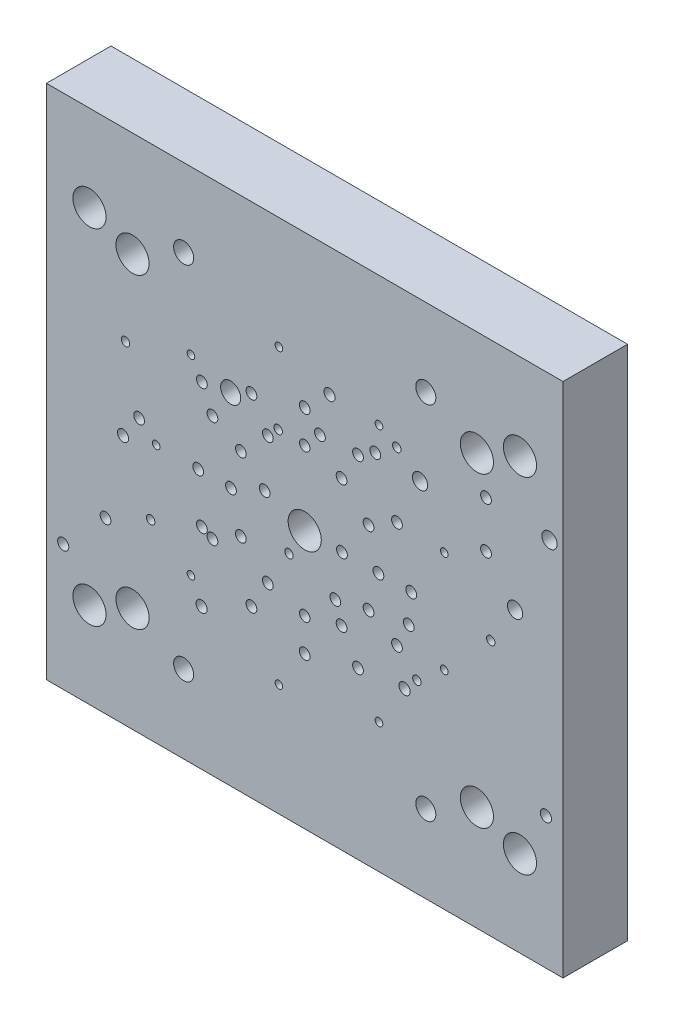
SolidWorks part; units mm, degrees
ref_plane "Front Plane" through (0, 0, 0) normal (0, 0, 1) x (1, 0, 0)
ref_plane "Top Plane" through (0, 0, 0) normal (0, 1, 0) x (1, 0, 0)
ref_plane "Right Plane" through (0, 0, 0) normal (1, 0, 0) x (0, 0, -1)
sketch "Sketch1" plane through (0, 0, 0) normal (0, 0, 1) x (1, 0, 0)
  line L1 (-152.4, 152.4) -> (152.4, 152.4)
  line L2 (-152.4, 152.4) -> (-152.4, -152.4)
  line L3 (-152.4, -152.4) -> (152.4, -152.4)
  line L4 (152.4, 152.4) -> (152.4, -152.4)
  line L5 (-152.4, 152.4) -> (152.4, -152.4) construction
  line L6 (-152.4, -152.4) -> (152.4, 152.4) construction
  point P0 (0, 0)
  dimension "D1" = 304.8
  dimension "D2" = 304.8
extrude "Boss-Extrude1" add sketch "Sketch1" along normal blind 38.1
sketch "Sketch2" plane through (0, 0, 38.1) normal (0, 0, 1) x (1, 0, 0)
  line L0 (-152.4, 0) -> (152.4, 0) construction
  line L5 (-152.4, 152.4) -> (-152.4, -152.4) construction
  line L6 (152.4, -152.4) -> (152.4, 152.4) construction
  line L7 (-152.4, -101.6) -> (152.4, -101.6) construction
  line L8 (-152.4, 101.6) -> (152.4, 101.6) construction
  line L9 (0, 101.6) -> (0, -101.6) construction
  line L10 (127, 101.6) -> (127, -101.6) construction
  line L11 (-127, 101.6) -> (-127, -101.6) construction
  circle A0 centre (-127, 101.6) radius 6.5151
  circle A1 centre (127, 101.6) radius 6.5151
  circle A2 centre (127, -101.6) radius 6.5151
  circle A3 centre (-127, -101.6) radius 6.5151
  circle A4 centre (0, 0) radius 6.5151
  dimension "D5" = 13.0302
  dimension "D1" = 101.6
  dimension "D2" = 101.6
  dimension "D3" = 127
  dimension "D4" = 127
extrude "HAAS T-Slot Holes" cut sketch "Sketch2" against normal through all
sketch "Sketch3" plane through (0, 0, 38.1) normal (0, 0, 1) x (1, 0, 0)
  circle A0 centre (-127, 101.6) radius 9.779
  circle A1 centre (127, 101.6) radius 9.779
  circle A2 centre (0, 0) radius 9.779
  circle A3 centre (127, -101.6) radius 9.779
  circle A4 centre (-127, -101.6) radius 9.779
  dimension "D1" = 19.558
extrude "HAAS Counter Bores" cut sketch "Sketch3" against normal offset from surface (22.225 mm away) 15.875 contours A0 | A1 | A2 | A3 | A4 up to face at (6.5151, 0, 0)
sketch "Sketch4" plane through (0, 0, 38.1) normal (0, 0, 1) x (1, 0, 0)
  line L0 (-127, 90.4875) -> (127, 90.4875) construction
  line L1 (-127, 30.1625) -> (127, 30.1625) construction
  line L2 (-127, 30.1625) -> (-127, -30.1625) construction
  line L3 (-127, -30.1625) -> (127, -30.1625) construction
  line L4 (127, 30.1625) -> (127, -30.1625) construction
  line L5 (-127, 30.1625) -> (127, -30.1625) construction
  line L6 (-127, -30.1625) -> (127, 30.1625) construction
  line L7 (-127, -90.4875) -> (127, -90.4875) construction
  line L8 (-101.6, 90.4875) -> (-101.6, 84.1375) construction
  line L9 (-101.6, -90.4875) -> (-101.6, -84.1375) construction
  line L10 (101.6, -90.4875) -> (101.6, -84.1375) construction
  line L11 (101.6, 90.4875) -> (101.6, 84.1375) construction
  circle A0 centre (-101.6, 90.4875) radius 6.5151
  circle A1 centre (101.6, 90.4875) radius 6.5151
  circle A2 centre (-101.6, -90.4875) radius 6.5151
  circle A3 centre (101.6, -90.4875) radius 6.5151
  point P0 (0, 0)
  dimension "D9" = 13.0302
  dimension "D1" = 60.325
  dimension "D2" = 254
  dimension "D5" = 203.2
  dimension "D6" = 25.4
  dimension "D7" = 203.2
  dimension "D8" = 6.35
  dimension "D3" = 60.325
  dimension "D4" = 60.325
extrude "Tormach T-Slot Holes" cut sketch "Sketch4" against normal through all
sketch "Sketch5" plane through (0, 0, 38.1) normal (0, 0, 1) x (1, 0, 0)
  circle A0 centre (-101.6, 90.4875) radius 9.779
  circle A1 centre (101.6, 90.4875) radius 9.779
  circle A2 centre (101.6, -90.4875) radius 9.779
  circle A3 centre (-101.6, -90.4875) radius 9.779
  dimension "D1" = 19.558
extrude "Tormach Counter bores" cut sketch "Sketch5" against normal up to surface (22.225 mm away) up to face at (-117.221, 101.6, 15.875)
sketch "Sketch6" plane through (0, 0, 38.1) normal (0, 0, 1) x (1, 0, 0)
  circle A0 centre (0, 0) radius 43.5 construction
  circle A1 centre (0, 43.5) radius 3.0734
  circle A2 centre (0, -43.5) radius 3.0734
  dimension "D1" = 87.0001
  dimension "D2" = 6.1468
extrude "Sprocket Locating Holes" cut sketch "Sketch6" against normal blind 6.35
sketch "Sketch7" plane through (0, 0, 38.1) normal (0, 0, 1) x (1, 0, 0)
  circle A0 centre (0, 0) radius 43.5 construction
  circle A2 centre (43.5, 0) radius 3.175
  circle A4 centre (37.6721, -21.75) radius 3.175
  circle A5 centre (21.75, -37.6721) radius 3.175
  circle A6 centre (0, -43.5) radius 3.175 [skipped]
  circle A7 centre (-21.75, -37.6721) radius 3.175
  circle A8 centre (-37.6721, -21.75) radius 3.175
  circle A9 centre (-43.5, 0) radius 3.175
  circle A10 centre (-37.6721, 21.75) radius 3.175
  circle A11 centre (-21.75, 37.6721) radius 3.175
  circle A12 centre (0, 43.5) radius 3.175 [skipped]
  circle A13 centre (21.75, 37.6721) radius 3.175
  circle A14 centre (37.6721, 21.75) radius 3.175
  point P31 (0, 0)
  dimension "D1" = 87.0001
  dimension "D2" = 6.35
  dimension "D3" = 12
extrude "Sprocket Mounting clearance holes" cut sketch "Sketch7" against normal blind 9.525
sketch "Sketch8" plane through (0, 0, 38.1) normal (0, 0, 1) x (1, 0, 0)
  line L1 (-71.4375, 106.4641) -> (71.4375, 106.4641) construction
  line L2 (-71.4375, 106.4641) -> (-71.4375, -106.4641) construction
  line L3 (-71.4375, -106.4641) -> (71.4375, -106.4641) construction
  line L4 (71.4375, 106.4641) -> (71.4375, -106.4641) construction
  line L5 (-71.4375, 106.4641) -> (71.4375, -106.4641) construction
  line L6 (-71.4375, -106.4641) -> (71.4375, 106.4641) construction
  circle A0 centre (-71.4375, 106.4641) radius 5.9182
  circle A1 centre (71.4375, 106.4641) radius 5.9182
  circle A2 centre (71.4375, -106.4641) radius 5.9182
  circle A3 centre (-71.4375, -106.4641) radius 5.9182
  point P0 (0, 0)
  dimension "D3" = 11.8364
  dimension "D1" = 142.875
  dimension "D2" = 212.9282
extrude "1/2-13 Tapped Holes" cut sketch "Sketch8" against normal blind 19.05
sketch "Sketch9" plane through (0, 0, 38.1) normal (0, 0, 1) x (1, 0, 0)
  circle A0 centre (-117.5189, -52.2876) radius 3.175
  circle A1 centre (-60.6634, -28.4101) radius 3.175
  circle A2 centre (-60.6634, 45.677) radius 3.175
  circle A3 centre (-23.6198, 8.6335) radius 3.175
  circle A4 centre (-97.707, 8.6335) radius 3.175
  circle A5 centre (18.0623, -26.1797) radius 3.175
  circle A6 centre (21.9762, 0) radius 3.175
  circle A7 centre (61.3833, -17.3739) radius 3.175
  circle A8 centre (106.976, 70.3959) radius 3.175
  circle A9 centre (106.976, 42.9004) radius 3.175
  circle A10 centre (144.4539, 67.4373) radius 4.5
  circle A11 centre (124.1092, 21.6131) radius 4.5
  circle A12 centre (68.0681, 59.3279) radius 4.5
  circle A13 centre (58.9353, -51.2652) radius 3.3
  circle A14 centre (-142.4923, -78.095) radius 3.3
  circle A15 centre (-105.7351, 43.7713) radius 2.5
  circle A16 centre (-90.8975, -39.8642) radius 2.5
  circle A17 centre (-9.2711, -16.3656) radius 2.5
  circle A18 centre (-15.6655, 43.8657) radius 2.5
  circle A20 centre (14.6267, 76.8405) radius 3.3
  circle A21 centre (8.9855, 53.4682) radius 3.175
  circle A22 centre (41.6559, 60.6579) radius 3.175
extrude "SSB Holes" cut sketch "Sketch9" against normal blind 19.05
ref_axis "Axis1" through (0, 0, 0) along (0, 0, 1)
sketch "Sketch10" plane through (0, 0, 38.1) normal (0, 0, 1) x (1, 0, 0)
  circle A0 centre (0, 0) radius 62.865 construction
  circle A1 centre (0, 62.865) radius 3.175
  circle A13 centre (31.4325, 54.4427) radius 3.175
  circle A14 centre (54.4427, 31.4325) radius 3.175
  circle A15 centre (62.865, 0) radius 3.175
  circle A16 centre (54.4427, -31.4325) radius 3.175
  circle A17 centre (31.4325, -54.4427) radius 3.175
  circle A18 centre (0, -62.865) radius 3.175
  circle A19 centre (-31.4325, -54.4427) radius 3.175
  circle A20 centre (-54.4427, -31.4325) radius 3.175
  circle A21 centre (-62.865, 0) radius 3.175
  circle A22 centre (-54.4427, 31.4325) radius 3.175
  circle A23 centre (-31.4325, 54.4427) radius 3.175
  point P30 (0, 0)
  point P56 (0, 0)
  dimension "D1" = 125.73
  dimension "D2" = 6.35
  dimension "D4" = 12
extrude "Sprocket Countersunk Holes" cut sketch "Sketch10" against normal blind 19.05
sketch "Sketch12" plane through (0, 0, 38.1) normal (0, 0, 1) x (1, 0, 0)
  circle A0 centre (-107.2144, -4.9977) radius 3.3
  circle A1 centre (-60.8212, -69.1392) radius 3.3
  circle A2 centre (142.3129, -74.567) radius 3.3
  circle A4 centre (54.3307, 69.7186) radius 2.4964
  circle A5 centre (109.7823, -1.2607) radius 2.5
  circle A6 centre (66.2094, -43.3332) radius 2.5
  circle A7 centre (-43.6886, 48.7489) radius 5.9182
  circle A8 centre (-71.4375, 106.4641) radius 5.9182 construction
extrude "DSB Holes" cut sketch "Sketch12" against normal blind 19.05
sketch "Brake Rotor Toe Clamp Holes" plane through (0, 0, 38.1) normal (0, 0, 1) x (1, 0, 0)
  line L0 (-74.6653, 106.6331) -> (74.6653, -106.6331) construction
  line L1 (74.6653, 106.6331) -> (-74.6653, -106.6331) construction
  line L6 (0, 0) -> (192.0367, 0) construction
  line L7 (0, 0) -> (-160.9096, 0) construction
  line L8 (0, 0) -> (0, 219.8313) construction
  line L9 (0, 0) -> (-215.8918, 38.0675) construction
  circle A0 centre (0, 0) radius 130.175 construction
  circle A10 centre (-87.63, 0) radius 2.3813 construction
  circle A12 centre (-74.93, 0) radius 2.3813 construction
  circle A13 centre (-80.0452, 14.1141) radius 2.3813
  circle A14 centre (-70.4112, 25.6276) radius 2.3812 construction
  circle A15 centre (-70.3905, 40.64) radius 2.3812 construction
  circle A16 centre (-82.3453, 29.9712) radius 2.3812 construction
  circle A17 centre (-57.3997, 48.1641) radius 2.3813 construction
  circle A18 centre (-52.2458, 62.2641) radius 2.3812
  circle A19 centre (-67.1285, 56.3275) radius 2.3812 construction
  circle A20 centre (-37.465, 64.8913) radius 2.3813 construction
  circle A21 centre (-27.7994, 76.3782) radius 2.3813 construction
  circle A22 centre (-43.815, 75.8898) radius 2.3813 construction
  circle A23 centre (-13.0115, 73.7916) radius 2.3813 construction
  circle A24 centre (0, 81.28) radius 2.3813
  circle A25 centre (-15.2168, 86.2987) radius 2.3813 construction
  circle A26 centre (13.0115, 73.7916) radius 2.3812 construction
  circle A27 centre (27.7994, 76.3782) radius 2.3812 construction
  circle A28 centre (15.2168, 86.2987) radius 2.3813 construction
  circle A29 centre (37.465, 64.8913) radius 2.3812 construction
  circle A30 centre (52.2458, 62.2641) radius 2.3813
  circle A31 centre (43.815, 75.8898) radius 2.3812 construction
  circle A32 centre (57.3997, 48.1641) radius 2.3813 construction
  circle A33 centre (70.3905, 40.64) radius 2.3813 construction
  circle A34 centre (67.1285, 56.3275) radius 2.3813 construction
  circle A35 centre (70.4112, 25.6276) radius 2.3813 construction
  circle A36 centre (80.0452, 14.1141) radius 2.3813
  circle A37 centre (82.3453, 29.9712) radius 2.3813 construction
  circle A38 centre (74.93, 0) radius 2.3813 construction
  circle A39 centre (80.0452, -14.1141) radius 2.3813 construction
  circle A40 centre (87.63, 0) radius 2.3813 construction
  circle A41 centre (70.4112, -25.6276) radius 2.3812 construction
  circle A42 centre (70.3905, -40.64) radius 2.3813
  circle A43 centre (82.3453, -29.9712) radius 2.3812 construction
  circle A44 centre (57.3997, -48.1641) radius 2.3813 construction
  circle A45 centre (52.2458, -62.2641) radius 2.3813 construction
  circle A46 centre (67.1285, -56.3275) radius 2.3812 construction
  circle A47 centre (37.465, -64.8913) radius 2.3813 construction
  circle A48 centre (27.7994, -76.3782) radius 2.3813
  circle A49 centre (43.815, -75.8898) radius 2.3813 construction
  circle A50 centre (13.0115, -73.7916) radius 2.3813 construction
  circle A51 centre (0, -81.28) radius 2.3812 construction
  circle A52 centre (15.2168, -86.2987) radius 2.3813 construction
  circle A53 centre (-13.0115, -73.7916) radius 2.3813 construction
  circle A54 centre (-27.7994, -76.3782) radius 2.3813
  circle A55 centre (-15.2168, -86.2987) radius 2.3813 construction
  circle A56 centre (-37.465, -64.8913) radius 2.3813 construction
  circle A57 centre (-52.2458, -62.2641) radius 2.3813 construction
  circle A58 centre (-43.815, -75.8898) radius 2.3812 construction
  circle A59 centre (-57.3997, -48.1641) radius 2.3813 construction
  circle A60 centre (-70.3905, -40.64) radius 2.3813
  circle A61 centre (-67.1285, -56.3275) radius 2.3813 construction
  circle A62 centre (-70.4112, -25.6276) radius 2.3813 construction
  circle A63 centre (-80.0452, -14.1141) radius 2.3813 construction
  circle A64 centre (-82.3453, -29.9712) radius 2.3813 construction
  point P27 (0, 0)
  point P130 (0, 0)
  dimension "D1" = 260.35
  dimension "D17" = 4.7625
  dimension "D18" = 81.28
  dimension "D19" = 18
  dimension "D14" = 4.7625
  dimension "D15" = 4.7625
  dimension "D10" = 55
  dimension "D11" = 55
  dimension "D12" = 87.63
  dimension "D13" = 12.7
  dimension "D16" = 10
hole_wizard "Rotor Clamp Bolts" positions "Sketch15" profile "Sketch16" hole size "M4" standard "AS"
sketch "Sketch15" plane through (0, 0, 38.1) normal (0, 0, 1) x (1, 0, 0)
  point P0 (-87.63, 0)
  point P3 (-67.1285, -56.3275)
  point P6 (-15.2168, -86.2987)
  point P9 (43.815, -75.8898)
  point P12 (82.3453, -29.9712)
  point P15 (82.3453, 29.9712)
  point P18 (43.815, 75.8898)
  point P21 (-15.2168, 86.2987)
  point P24 (-67.1285, 56.3275)
sketch "Sketch16" plane through (-87.63, 0, 38.1) normal (1, 0, 0) x (0, -1, 0)
  line L0 (0, 0) -> (0, 20.4019)
  line L1 (0, 20.4019) -> (2.25, 19.05)
  line L2 (2.25, 19.05) -> (2.25, 0)
  line L5 (2.25, 0) -> (0, 0)
  line L10 (0, 20.4019) -> (-2.25, 19.05) construction
  line L11 (0, -6.35) -> (0, 107.95) construction
  dimension "Hole Dia." = 4.5
  dimension "Hole Depth" = 19.05
  dimension "Drill Angle" = 118
equation "\"boltRotor\"=0.75"
equation "\"bolt\"=0.51159"
